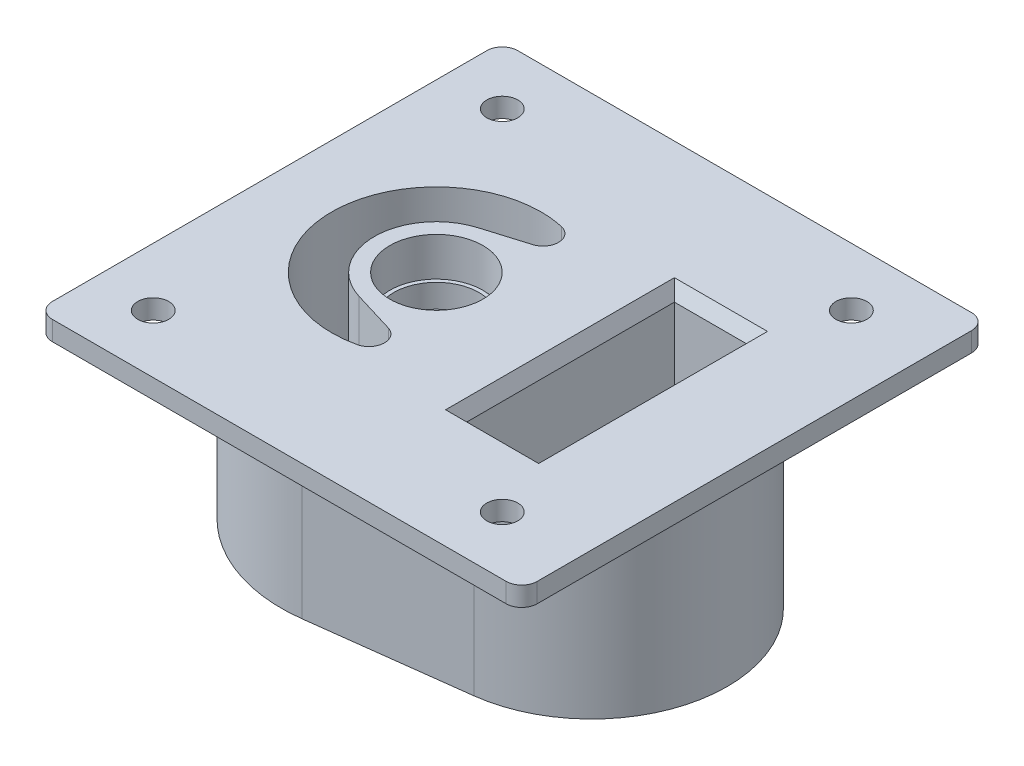
SolidWorks part; units mm, degrees
ref_plane "前视基准面" through (0, 0, 0) normal (0, 0, 1) x (1, 0, 0)
ref_plane "上视基准面" through (0, 0, 0) normal (0, 1, 0) x (1, 0, 0)
ref_plane "右视基准面" through (0, 0, 0) normal (1, 0, 0) x (0, 0, -1)
other "Configuration Table"
sketch "草图1" plane through (0, 0, 0) normal (0, 1, 0) x (1, 0, 0)
  line L0 (5, 39.6863) -> (44.375, 34.7255)
  line L1 (5, -39.6863) -> (44.375, -34.7255)
  arc A0 (5, 39.6863) -> (5, -39.6863) centre (0, 0) ccw
  arc A1 (44.375, -34.7255) -> (44.375, 34.7255) centre (40, 0) ccw
  dimension "D1" = 80
  dimension "D2" = 70
  dimension "D3" = 40
extrude "凸台-拉伸1" add sketch "草图1" along normal blind 55
sketch "草图2" plane through (0, 55, 0) normal (0, 1, 0) x (1, 0, 0)
  line L0 (-43, 60) -> (-43, -60)
  line L1 (-43, -60) -> (82, -60)
  line L2 (82, -60) -> (82, 60)
  line L3 (82, 60) -> (-43, 60)
  line L4 (-85.1462, 0) -> (135.373, 0) construction
  line L5 (4.625, -36.7098) -> (44, -31.749)
  line L6 (44, 31.749) -> (4.625, 36.7098)
  line L7 (5, -39.6863) -> (44.375, -34.7255)
  line L8 (44.375, 34.7255) -> (5, 39.6863)
  line L9 (5, -39.6863) -> (44.375, -34.7255)
  line L10 (44.375, 34.7255) -> (5, 39.6863)
  circle A0 centre (-28, 45) radius 4
  circle A1 centre (62, 45) radius 4
  circle A2 centre (62, -45) radius 4
  circle A3 centre (-28, -45) radius 4
  arc A4 (4.625, 36.7098) -> (4.625, -36.7098) centre (0, 0) ccw
  arc A5 (44, -31.749) -> (44, 31.749) centre (40, 0) ccw
  arc A6 (5, 39.6863) -> (5, -39.6863) centre (0, 0) ccw
  arc A7 (44.375, -34.7255) -> (44.375, 34.7255) centre (40, 0) ccw
  arc A8 (5, 39.6863) -> (5, -39.6863) centre (0, 0) ccw
  arc A9 (44.375, -34.7255) -> (44.375, 34.7255) centre (40, 0) ccw
  point P4 (-43, 0)
  arc M4 (5, 39.6863) -> (5, -39.6863) centre (0, 0) ccw
  line M5 (5, -39.6863) -> (44.375, -34.7255)
  arc M6 (44.375, -34.7255) -> (44.375, 34.7255) centre (40, 0) ccw
  line M7 (44.375, 34.7255) -> (5, 39.6863)
  dimension "D4" = 8
  dimension "D5" = 8
  dimension "D6" = 8
  dimension "D7" = 15
  dimension "D8" = 90
  dimension "D1" = 125
  dimension "D2" = 120
  dimension "D3" = 43
  dimension "D9" = 90
  dimension "D10" = 0
  dimension "D11" = 3
extrude "凸台-拉伸2" add sketch "草图2" against normal blind 5 separate body contours L4 L0 L1 L2 A3 A2 M6 M5 M4 | L0 L4 L2 L3 A0 A1 M4 M7 M6 | L4 A8 A5 L5 A4 M5 M6 | L4 A4 L6 A5 A9 M4 M7 region at (22.763, 55, -42.5852) region at (22.763, 55, 42.5852) region at (-25.6522, 55, -29.0868) region at (-38.5, 55, 1.2176)
sketch "草图6" plane through (0, 0, 0) normal (0, -1, 0) x (1, 0, 0)
  line L0 (4.75, -37.702) -> (44.125, -32.7412)
  line L1 (44.125, 32.7412) -> (4.75, 37.702)
  line L2 (5, -39.6863) -> (44.375, -34.7255)
  line L3 (44.375, 34.7255) -> (5, 39.6863)
  line L4 (5, -39.6863) -> (44.375, -34.7255)
  line L5 (44.375, 34.7255) -> (5, 39.6863)
  arc A0 (4.75, 37.702) -> (4.75, -37.702) centre (0, 0) ccw
  arc A1 (44.125, -32.7412) -> (44.125, 32.7412) centre (40, 0) ccw
  arc A2 (5, 39.6863) -> (5, -39.6863) centre (0, 0) ccw
  arc A3 (44.375, -34.7255) -> (44.375, 34.7255) centre (40, 0) ccw
  arc A4 (5, 39.6863) -> (5, -39.6863) centre (0, 0) ccw
  arc A5 (44.375, -34.7255) -> (44.375, 34.7255) centre (40, 0) ccw
  dimension "D1" = 0
  dimension "D2" = 2
extrude "切除-拉伸2" cut sketch "草图6" against normal blind 10 contours L0 A1 L1 A0 region at (16.3329, 0, 0)
sketch "草图4" plane through (0, 10, 0) normal (0, -1, 0) x (1, 0, 0)
  circle A0 centre (0, 0) radius 27
  dimension "D1" = 54
extrude "切除-拉伸1" cut sketch "草图4" against normal through all
sketch "草图5" plane through (0, 10, 0) normal (0, -1, 0) x (1, 0, 0)
  circle A0 centre (0, 0) radius 29
  dimension "D1" = 58
extrude "切除-拉伸3" cut sketch "草图5" against normal blind 4
sketch "草图8" plane through (0, 10, 0) normal (0, -1, 0) x (-1, 0, 0)
  circle A0 centre (-43.8748, 10) radius 7
  dimension "D1" = 14
  dimension "D2" = 45
  dimension "D3" = 10
extrude "切除-拉伸4" cut sketch "草图8" against normal through all
sketch "草图7" plane through (0, 10, 0) normal (0, -1, 0) x (1, 0, 0)
  line L0 (43.8748, -10) -> (43.8748, 3.0914) construction
  line L1 (38.8748, 24.75) -> (38.8748, -24.75) construction
  line L2 (38.8748, -24.75) -> (48.8748, -24.75) construction
  line L3 (48.8748, -24.75) -> (48.8748, 24.75) construction
  line L4 (48.8748, 24.75) -> (38.8748, 24.75) construction
  circle A0 centre (38.8748, 24.75) radius 2.25
  circle A1 centre (48.8748, 24.75) radius 2.25
  circle A2 centre (48.8748, -24.75) radius 2.25
  circle A3 centre (38.8748, -24.75) radius 2.25
  dimension "D2" = 4.5
  dimension "D3" = 4.5
  dimension "D4" = 4.5
  dimension "D5" = 14.75
  dimension "D1" = 10
  dimension "D6" = 49.5
extrude "切除-拉伸5" cut sketch "草图7" against normal through all
sketch "草图10" plane through (0, 55, 0) normal (0, 1, 0) x (1, 0, 0)
  line L0 (33.8748, 19.85) -> (33.8748, -20.15)
  line L1 (33.8748, -20.15) -> (53.8748, -20.15)
  line L2 (53.8748, -20.15) -> (53.8748, 19.85)
  line L3 (53.8748, 19.85) -> (33.8748, 19.85)
  line L4 (33.8748, 10) -> (53.8748, 10) construction
  line L5 (43.8748, 19.85) -> (43.8748, -20.15) construction
  line L6 (38.8748, 24.75) -> (38.8748, -24.75) construction
  circle A0 centre (43.8748, 10) radius 7 construction
  point P11 (43.8748, 10)
  dimension "D1" = 20
  dimension "D2" = 40
  dimension "D3" = 9.85
extrude "切除-拉伸6" cut sketch "草图10" against normal offset from surface (41 mm away) 4 up to face at (38.8748, 10, 22.5)
sketch "草图11" plane through (0, 55, 0) normal (0, 1, 0) x (1, 0, 0)
  line L0 (33.8748, 27.5) -> (33.8748, -27.5)
  line L1 (53.8748, -27.5) -> (53.8748, 27.5)
  line L2 (53.8748, 27.5) -> (33.8748, 27.5)
  line L3 (33.8748, -27.5) -> (53.8748, -27.5)
  line L4 (5, -39.6863) -> (44.375, -34.7255) construction
  line L5 (38.8748, 24.75) -> (38.8748, -24.75) construction
  line L6 (43.8748, 23.2972) -> (43.8748, -34.7885) construction
  line L7 (48.8748, 24.75) -> (48.8748, -24.75) construction
  point P2 (33.8748, 0)
  dimension "D1" = 55
  dimension "D2" = 20
  dimension "D3" = 5
extrude "切除-拉伸7" cut sketch "草图11" against normal offset from surface (31.5 mm away) 9.5 up to face at (43.8748, 14, 0.15)
sketch "草图12" plane through (0, 10, 0) normal (0, -1, 0) x (1, 0, 0)
  circle A0 centre (38.8748, 24.75) radius 3.75
  circle A1 centre (48.8748, 24.75) radius 3.75
  circle A2 centre (48.8748, -24.75) radius 3.75
  circle A3 centre (38.8748, -24.75) radius 3.75
  dimension "D1" = 7.5
  dimension "D2" = 7.5
  dimension "D3" = 7.5
  dimension "D4" = 7.5
extrude "切除-拉伸8" cut sketch "草图12" against normal blind 4.5
chamfer "倒角1" distance 2 angle 60 2 edges at (43.8748, 23.5, -19.85) (43.8748, 23.5, 20.15) first distance on face at (48.8748, 23.5, -27) first distance on face at (38.8748, 23.5, 22.5)
sketch "草图13" plane through (0, 55, 0) normal (0, -1, 0) x (-1, 0, 0)
  line L0 (-53.1194, 0) -> (22.5445, 0) construction
  line L1 (-27.2764, 25) -> (4.6471, 15.3103)
  line L2 (-27.2764, -25) -> (4.6471, -15.3103)
  line L3 (-27.2764, -25) -> (-27.2764, 25)
  circle A0 centre (0, 0) radius 16
  arc A2 (-4.625, -36.7098) -> (-4.625, 36.7098) centre (0, 0) ccw construction
  circle M32 centre (0, 0) radius 27
  dimension "D1" = 32
  dimension "D2" = 50
extrude "凸台-拉伸3" add sketch "草图13" along normal blind 20 contours L0 L2 A0 | L3 L0 A0 L1 | L0 L1 A0 M32 | L0 A0 L2 M32 region at (16.8612, 55, -11.0057) region at (16.8612, 55, 11.0057) region at (0, 55, -6.7906) region at (0, 55, 6.7906)
ref_plane "基准面1" through (0, 0, -49) normal (0, 0, 1) x (1, 0, 0)
ref_plane "基准面2" through (0, 0, -59) normal (0, 0, 1) x (1, 0, 0)
sketch "草图14" plane through (0, 55, 0) normal (0, -1, 0) x (-1, 0, 0)
  circle A1 centre (0, 0) radius 12
  dimension "D1" = 24
extrude "切除-拉伸9" cut sketch "草图14" along normal blind 10
sketch "草图15" plane through (0, 45, 0) normal (0, 1, 0) x (1, 0, 0)
  circle A0 centre (0, 0) radius 11
  dimension "D1" = 22
extrude "切除-拉伸10" cut sketch "草图15" against normal blind 6
sketch "草图16" plane through (0, 39, 0) normal (0, 1, 0) x (1, 0, 0)
  circle A0 centre (0, 0) radius 9
  dimension "D1" = 18
extrude "切除-拉伸11" cut sketch "草图16" against normal through all
fillet "圆角1" radius 4 7 edges at (27, 35, 0) (16.1639, 45, -21.627) (16.1639, 45, 21.627) (-43, 52.5, -60) (-43, 52.5, 60) (82, 52.5, -60) (82, 52.5, 60)
chamfer "倒角2" distance 2 angle 60 4 edges at (33.8748, 55, 0) (43.8748, 55, 27.5) (43.8748, 55, -27.5) (53.8748, 55, 0) first distance on face at (0, 55, -12)
fillet "圆角2" radius 2 4 edges at (75, 50, 0) (24.6875, 50, -37.2059) (-40, 50, 0) (24.6875, 50, 37.2059)
